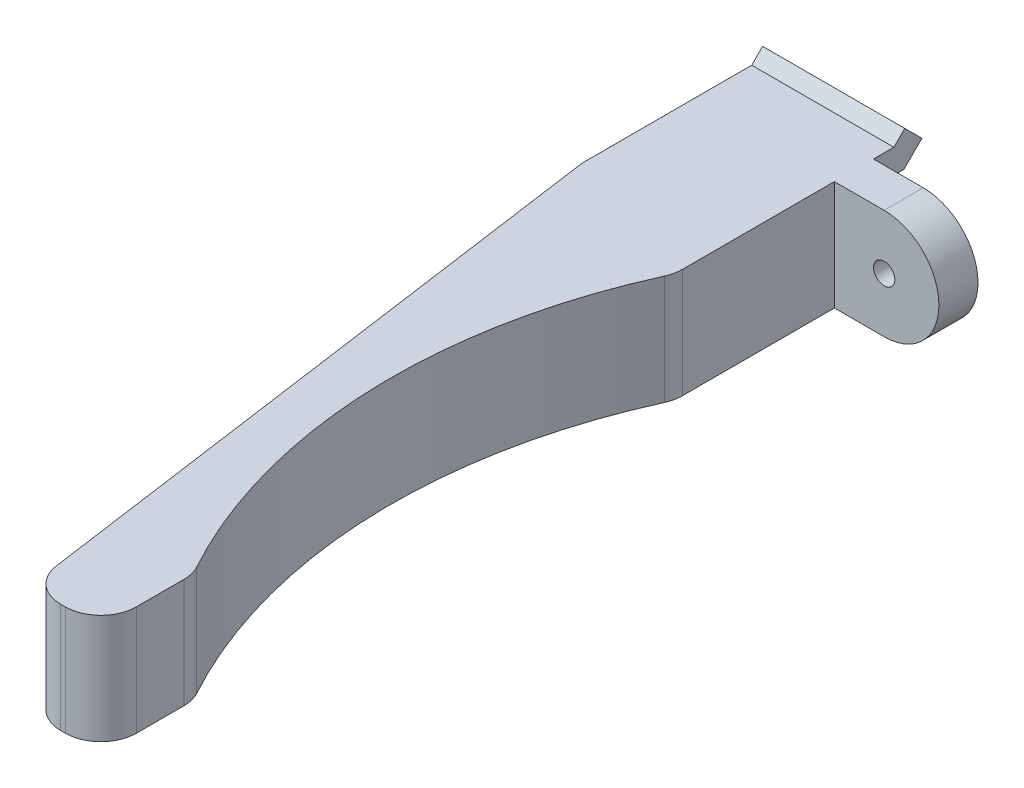
SolidWorks part; units mm, degrees
ref_plane "Front Plane" through (0, 0, 0) normal (0, 0, 1) x (1, 0, 0)
ref_plane "Top Plane" through (0, 0, 0) normal (0, 1, 0) x (1, 0, 0)
ref_plane "Right Plane" through (0, 0, 0) normal (1, 0, 0) x (0, 0, -1)
sketch "Sketch2" plane through (0, 0, 0) normal (0, 0, 1) x (1, 0, 0)
  line L0 (0, 5.9203) -> (0, 8.9503) construction
  line L1 (-5, -5.8182) -> (5, -5.8182)
  line L2 (-5, -5.8182) -> (-5, 8.9503)
  line L3 (-5, 8.9503) -> (5, 8.9503)
  line L4 (5, -5.8182) -> (5, 8.9503)
  line L7 (26.9339, 5.9203) -> (-4.6913, 5.9203) construction
  line L8 (0, -5.8182) -> (0, -2.7882) construction
  point P0 (0, 0)
  dimension "D1" = 10
extrude "Boss-Extrude1" add sketch "Sketch2" along normal blind 5
sketch "Sketch8" plane through (-5, 0, 0) normal (-1, 0, 0) x (0, 0, 1)
  line L6 (-0.15, 5.7703) -> (0, 5.7703)
  line L7 (0, 8.9503) -> (0, -5.8182) construction
  line L8 (0, 5.7703) -> (0, 4.0703)
  line L9 (0, 4.0703) -> (-0.15, 4.0703)
  line L11 (-0.15, -1.9297) -> (0, -1.9297)
  line L12 (-2.1379, 4.0703) -> (-0.15, 4.0703)
  line L13 (-0.15, 4.0703) -> (-0.15, 5.7703)
  line L14 (-0.15, 5.7703) -> (-1.4337, 5.7703)
  line L15 (-1.4337, 5.7703) -> (-2.2, 6.5366)
  line L16 (-2.2, 6.5366) -> (-3.4021, 5.3345)
  line L17 (-3.4021, 5.3345) -> (-2.1379, 4.0703)
  line L18 (-2.1379, 4.0703) -> (-0.15, 4.0703)
  line L20 (-0.15, 5.7703) -> (-1.4337, 5.7703)
  line L21 (-1.4337, 5.7703) -> (-2.2, 6.5366)
  line L22 (-2.2, 6.5366) -> (-3.4021, 5.3345)
  line L23 (-3.4021, 5.3345) -> (-2.1379, 4.0703)
  line L24 (-2.1379, -1.9297) -> (-0.15, -1.9297)
  line L25 (-0.15, -1.9297) -> (-0.15, -0.2297)
  line L26 (-0.15, -0.2297) -> (-1.4337, -0.2297)
  line L27 (-1.4337, -0.2297) -> (-2.2, 0.5366)
  line L28 (-2.2, 0.5366) -> (-3.4021, -0.6655)
  line L29 (-3.4021, -0.6655) -> (-2.1379, -1.9297)
  line L30 (-2.1379, -1.9297) -> (-0.15, -1.9297)
  line L32 (-0.15, -0.2297) -> (-1.4337, -0.2297)
  line L33 (-1.4337, -0.2297) -> (-2.2, 0.5366)
  line L34 (-2.2, 0.5366) -> (-3.4021, -0.6655)
  line L35 (-3.4021, -0.6655) -> (-2.1379, -1.9297)
  line L37 (-0.15, -0.2297) -> (0, -0.2297)
  line L38 (0, -1.9297) -> (0, -0.2297)
  dimension "D1" = 0.15
  dimension "D2" = 0.15
extrude "Boss-Extrude4" add sketch "Sketch8" against normal up to surface (10 mm away) up to face at (5, 1.566, 2.5)
sketch "Sketch9" plane through (0, 0, 0) normal (0, 0, -1) x (-1, 0, 0)
  line L4 (-5, 8.9503) -> (-5, 5.7703)
  line L5 (-5, 5.7703) -> (5, 5.7703)
  line L6 (5, 5.7703) -> (5, 8.9503)
  line L7 (5, 8.9503) -> (-5, 8.9503)
  line L8 (-5, 8.9503) -> (-5, 5.7703)
  line L10 (5, 5.7703) -> (5, 8.9503)
  line L11 (5, 8.9503) -> (-5, 8.9503)
  line L16 (5, -1.9297) -> (-5, -1.9297)
  line L17 (-5, -1.9297) -> (-5, -5.8182)
  line L18 (-5, -5.8182) -> (5, -5.8182)
  line L19 (5, -5.8182) -> (5, -1.9297)
  line L21 (-5, -1.9297) -> (-5, -5.8182)
  line L22 (-5, -5.8182) -> (5, -5.8182)
  line L23 (5, -5.8182) -> (5, -1.9297)
  line L26 (-5, 5.7703) -> (5, 5.7703)
  line L27 (5, -1.9297) -> (-5, -1.9297)
  dimension "D1" = 0
  dimension "D2" = 0
extrude "Cut-Extrude3" cut sketch "Sketch9" against normal blind 5
sketch "Sketch10" plane through (0, 5.7703, 0) normal (0, 1, 0) x (1, 0, 0)
  line L0 (-5, -5) -> (-5, -10.5)
  line L1 (-5, -10.5) -> (1.3524, -55.7)
  line L2 (1.3524, -55.7) -> (6.3524, -55.7)
  line L3 (-5, -5) -> (5, -5)
  line L4 (-120.9789, 453.7107) -> (412.3545, 453.7107) construction
  line L5 (6.3524, -55.7) -> (6.3524, -49.2)
  line L6 (5, -5) -> (5, -14)
  arc A1 (5, -14) -> (6.3524, -49.2) centre (39.6089, -30.2962) ccw
  dimension "D1" = 172
  dimension "D2" = 45.2
  dimension "D3" = 5
  dimension "D4" = 6.5
  dimension "D5" = 5.5
  dimension "D6" = 9
extrude "Boss-Extrude5" add sketch "Sketch10" against normal up to surface (7.7 mm away) up to face at (0, -1.9297, 1.4311)
ref_plane "Plane1" through (0, 0, 2.75) normal (0, 0, 1) x (1, 0, 0)
sketch "Sketch12" plane through (0, 0, 0) normal (0, 0, 1) x (1, 0, 0)
  line L0 (5, 5.7703) -> (8.5, 5.7703)
  line L1 (8.5, -1.9297) -> (5, -1.9297)
  line L2 (5, -1.9297) -> (5, 5.7703)
  line L3 (1.3524, 5.7703) -> (6.3524, 5.7703) construction
  line L4 (1.3524, -1.9297) -> (6.3524, -1.9297) construction
  line L5 (5, 5.3345) -> (5, 6.5366) construction
  line L6 (6.3524, 5.7703) -> (1.3552, 5.7703) construction
  arc A0 (8.5, 5.7703) -> (8.5, -1.9297) centre (8.5, 1.9203) cw
  circle A1 centre (8.5, 1.9203) radius 0.75
  dimension "D1" = 1.5
  dimension "D2" = 3.5
extrude "Boss-Extrude7" add sketch "Sketch12" along normal up to surface (2.75 mm away) up to plane "Plane1"
fillet "Fillet1" radius 2.5 4 edges at (6.3524, 1.9203, 55.7) (1.3524, 1.9203, 55.7) (6.3524, 1.9203, 49.2) (5, 1.9203, 14)
